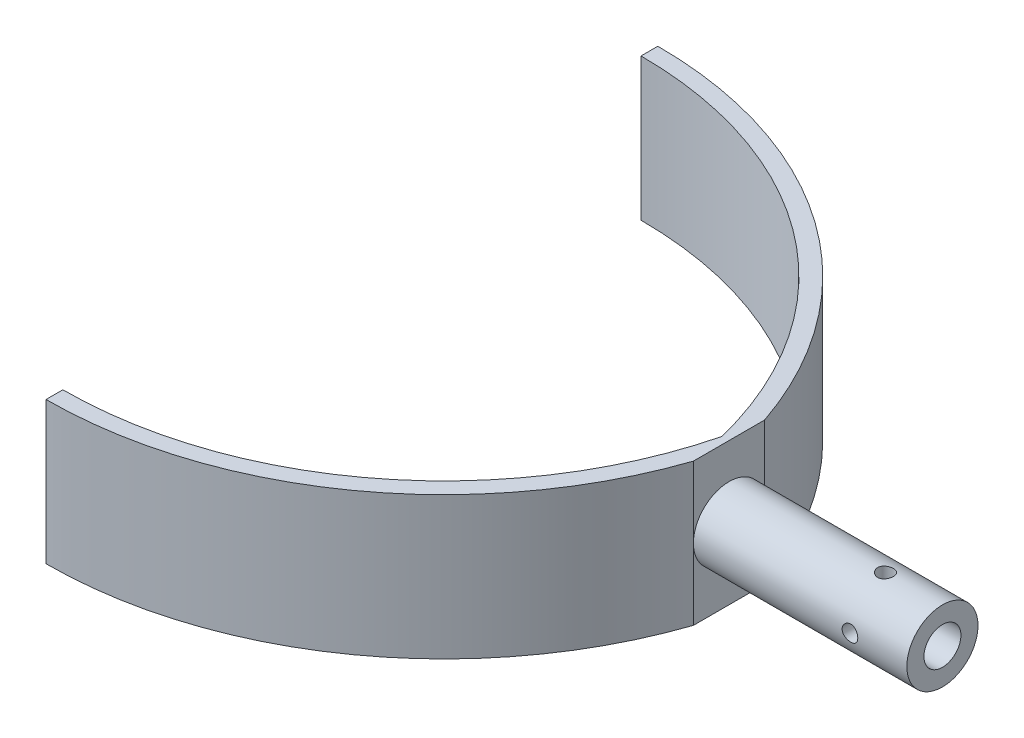
SolidWorks part; units mm, degrees
ref_plane "Front Plane" through (0, 0, 0) normal (0, 0, 1) x (1, 0, 0)
ref_plane "Top Plane" through (0, 0, 0) normal (0, 1, 0) x (1, 0, 0)
ref_plane "Right Plane" through (0, 0, 0) normal (1, 0, 0) x (0, 0, -1)
sketch "Sketch1" plane through (0, 0, 0) normal (1, 0, 0) x (0, 0, -1)
  circle A0 centre (0, 0) radius 5
  dimension "D1" = 10
  dimension "D2" = 0
  dimension "D3" = 0
extrude "Boss-Extrude1" add sketch "Sketch1" along normal blind 25
sketch "Sketch2" plane through (0, 0, 0) normal (-1, 0, 0) x (0, 0, 1)
  circle A0 centre (0, 0) radius 2.6
  dimension "D1" = 5.2
extrude "Cut-Extrude1" cut sketch "Sketch2" against normal blind 25
sketch "Sketch3" plane through (0, 0, 0) normal (0, 1, 0) x (1, 0, 0)
  line L0 (25, -5) -> (25, 5) construction
  circle A0 centre (17, 0) radius 1.1
  dimension "D1" = 2.2
  dimension "D2" = 8
  dimension "D3" = 0
extrude "Cut-Extrude3" cut sketch "Sketch3" against normal blind 25 and the other way blind 25 contours A0
sketch "Sketch4" plane through (0, 0, 0) normal (0, 0, 1) x (1, 0, 0)
  line L0 (25, -5) -> (25, 5) construction
  circle A0 centre (17, 0) radius 1.1
  dimension "D1" = 2.2
  dimension "D2" = 0
  dimension "D3" = 8
extrude "Cut-Extrude4" cut sketch "Sketch4" against normal blind 25 and the other way blind 25
sketch "Sketch6" plane through (0, 0, 0) normal (-1, 0, 0) x (0, 0, 1)
  circle A0 centre (0, 0) radius 5
extrude "Boss-Extrude3" add sketch "Sketch6" along normal blind 5
sketch "Sketch5" plane through (0, 0, 0) normal (0, 1, 0) x (1, 0, 0)
  line L1 (-58, -43) -> (-58, -40.634)
  line L2 (-5, 5) -> (-5, -5)
  line L3 (-58, 40.634) -> (-58, 43)
  line L4 (-5, -5) -> (-5, 5)
  line L5 (-5, -5) -> (-5, 5)
  line L6 (-5, -5) -> (-5, 5)
  arc A0 (-5, 5) -> (-58, -40.634) centre (-58, 12.9605) cw
  arc A1 (-5, -5) -> (-58, -43) centre (-58, 12.9605) cw
  arc A2 (-5, 5) -> (-58, 43) centre (-58, -12.9605) ccw
  arc A3 (-5, -5) -> (-58, 40.634) centre (-58, -12.9605) ccw
  arc A4 (-58, 40.634) -> (-5, -5) centre (-58, -12.9605) cw
  arc A5 (-58, 43) -> (-5, 5) centre (-58, -12.9605) cw
  dimension "D2" = 0
  dimension "D6" = 0
  dimension "D1" = 0
  dimension "D4" = 0
  dimension "D5" = 0
  dimension "D7" = 0
  dimension "D8" = 43
  dimension "D9" = 0
  dimension "D10" = 0
  dimension "D11" = 0
  dimension "D12" = 0
extrude "Boss-Extrude2" add sketch "Sketch5" along normal blind 10 and the other way blind 10 contours A3 A0 A2 L3 | A1 A3 A0 L1 | A3 L2 A0 region at (-57.3175, 0, 41.817) region at (-5.3192, 0, 0) region at (-24.5816, 0, -29.8087)
